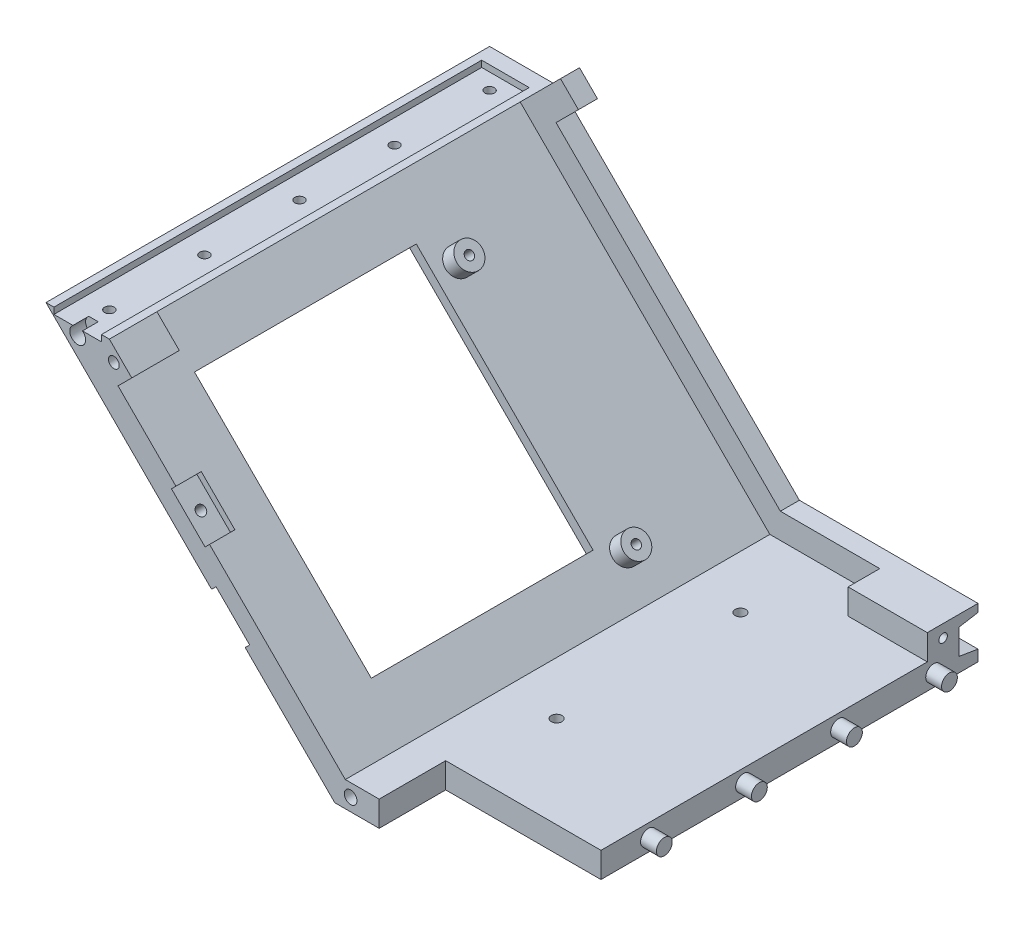
SolidWorks part; units mm, degrees
ref_plane "Plan de face" through (0, 0, 0) normal (0, 0, 1) x (1, 0, 0)
ref_plane "Plan de dessus" through (0, 0, 0) normal (0, 1, 0) x (1, 0, 0)
ref_plane "Plan de droite" through (0, 0, 0) normal (1, 0, 0) x (0, 0, -1)
sketch "Main-Sketch" plane through (0, 0, 0) normal (0, 0, 1) x (1, 0, 0)
  line L0 (0, 0) -> (0, 8)
  line L1 (0, 8) -> (-59.6863, 8)
  line L2 (-59.6863, 8) -> (-138.4931, 86.8069)
  line L3 (-154.15, 91.15) -> (-134.15, 91.15)
  line L4 (-154.15, 91.15) -> (-63, 0)
  line L5 (-63, 0) -> (0, 0)
  line L8 (-134.15, 91.15) -> (-138.4931, 86.8069)
  dimension "D1" = 8
  dimension "D2" = 8
  dimension "D3" = 63
  dimension "D4" = 135
  dimension "D5" = 20
  dimension "D6" = 154.15
extrude "Main-Extrusion" add sketch "Main-Sketch" along normal blind 140
sketch "Lcd-Sketch" plane through (0, 0, 0) normal (0, -1, 0) x (1, 0, 0)
  line L1 (0, 140) -> (-49, 140)
  line L2 (0, 140) -> (0, 119)
  line L3 (0, 119) -> (-49, 119)
  line L4 (-49, 140) -> (-49, 119)
  dimension "D1" = 21
  dimension "D2" = 49
extrude "Lcd-Hole" cut sketch "Lcd-Sketch" against normal through all
sketch "MotorBoard-Hole-Sketch" plane through (-31.5, -31.5, 0) normal (-0.7071, -0.7071, 0) x (0, 0, 1)
  line L0 (0, 173.4533) -> (0, 44.5477) construction
  line L1 (120, 143.4533) -> (50, 143.4533)
  line L2 (120, 143.4533) -> (120, 64.5477)
  line L3 (120, 64.5477) -> (50, 64.5477)
  line L4 (50, 143.4533) -> (50, 64.5477)
  line L5 (140, 173.4533) -> (140, 44.5477) construction
  line L6 (140, 173.4533) -> (0, 173.4533) construction
  line L7 (140, 44.5477) -> (0, 44.5477) construction
  dimension "D1" = 50
  dimension "D2" = 20
  dimension "D3" = 30
  dimension "D4" = 20
extrude "MotorBoard-Hole" cut sketch "MotorBoard-Hole-Sketch" against normal through all
sketch "MotorBoard-Window-Sketch" plane through (-31.5, -31.5, 0) normal (-0.7071, -0.7071, 0) x (0, 0, 1)
  line L0 (120, 64.5477) -> (120, 143.4533) construction
  line L1 (128, 151.4533) -> (42, 151.4533)
  line L2 (128, 151.4533) -> (128, 56.5477)
  line L3 (128, 56.5477) -> (42, 56.5477)
  line L4 (42, 151.4533) -> (42, 56.5477)
  line L5 (120, 143.4533) -> (50, 143.4533) construction
  line L6 (50, 143.4533) -> (50, 64.5477) construction
  line L7 (50, 64.5477) -> (120, 64.5477) construction
  dimension "D1" = 8
  dimension "D2" = 8
  dimension "D3" = 8
  dimension "D4" = 8
extrude "MotorBoard-Window" cut sketch "MotorBoard-Window-Sketch" against normal blind 5
sketch "MotorBoard-Fix-Sketch" plane through (-25.8431, -25.8431, 0) normal (0.7071, 0.7071, 0) x (0, 0, -1)
  line L0 (-140, 47.8614) -> (-140, 159.3112) construction
  line L1 (-140, 47.8614) -> (0, 47.8614) construction
  circle A0 centre (-42.5, 60.8614) radius 4
  circle A1 centre (-42.5, 135.3614) radius 4
  dimension "D1" = 8
  dimension "D2" = 74.5
  dimension "D3" = 97.5
  dimension "D4" = 13
extrude "MotorBoard-Fix-Extrusion" add sketch "MotorBoard-Fix-Sketch" along normal blind 5
sketch "MotorBoard-Fix-Hole-Sketch" plane through (-22.3076, -22.3076, 0) normal (0.7071, 0.7071, 0) x (0, 0, -1)
  circle A0 centre (-42.5, 60.8614) radius 1.35
  circle A1 centre (-42.5, 135.3614) radius 1.35
  circle A2 centre (-42.5, 135.3614) radius 4 construction
  dimension "D1" = 2.7
extrude "MotorBoard-Fix-Hole" cut sketch "MotorBoard-Fix-Hole-Sketch" against normal through all
hole_wizard "Fraisage pour vis à tête fraisée M32" positions "Esquisse8" profile "Esquisse9" countersink size "M3" standard "Ansi Metric" end condition through all
sketch "Esquisse8" plane through (0, 0, 0) normal (0, -1, 0) x (-1, 0, 0)
  line L2 (63, -140) -> (49, -140) construction
  line L4 (63, -140) -> (63, 0) construction
  line L5 (0, -119) -> (0, 0) construction
  point P0 (43, -90)
  point P2 (43, -32)
  dimension "D1" = 58
  dimension "D2" = 20
  dimension "D3" = 50
  dimension "D4" = 43
sketch "Esquisse9" plane through (-43, 0, 90) normal (1, 0, 0) x (0, 0, -1)
  line L0 (0, 0) -> (0, 91.15)
  line L1 (0, 91.15) -> (1.7, 91.15)
  line L2 (1.7, 91.15) -> (1.7, 1.45)
  line L3 (1.7, 1.45) -> (3.15, 0)
  line L5 (3.15, 0) -> (0, 0)
  line L6 (-1.7, 1.45) -> (-3.15, 0) construction
  line L11 (0, -6.35) -> (0, 107.95) construction
  dimension "Diamètre du perçage jusqu'au prochain" = 3.4
  dimension "Profondeur du perçage jusqu'au prochain" = 91.15
  dimension "Diamètre du fraisage entrant" = 6.3
  dimension "Angle du fraisage entrant" = 90
sketch "Bottom-Reinforcement-Sketch" plane through (0, 0, 0) normal (0, 0, -1) x (-1, 0, 0)
  line L0 (0, 8) -> (0, 16)
  line L1 (0, 16) -> (56.3726, 16)
  line L2 (56.3726, 16) -> (127.1794, 86.8069)
  line L3 (127.1794, 86.8069) -> (120.1084, 93.8779)
  line L4 (120.1084, 93.8779) -> (125.7652, 99.5348)
  line L5 (125.7652, 99.5348) -> (138.4931, 86.8069)
  line L6 (138.4931, 86.8069) -> (59.6863, 8)
  line L7 (59.6863, 8) -> (0, 8)
  point P4 (138.4931, 86.8069)
  point P12 (118.4675, 105.9273)
  point P14 (105.4642, 93.374)
  point P15 (109.6976, 86.8069)
  point P16 (0, 0)
  point P17 (122.9622, 79.545)
  point P18 (50.4301, 16)
  point P19 (113.6488, 84.3428)
  dimension "D1" = 8
  dimension "D2" = 8
  dimension "D3" = 10
  dimension "D4" = 8
extrude "Bottom-Reinforcement-Extrusion" add sketch "Bottom-Reinforcement-Sketch" against normal blind 6 separate body
sketch "LeftFix-Sketch" plane through (0, 0, 0) normal (1, 0, 0) x (0, 0, -1)
  line L0 (0, 0) -> (0, 8) construction
  line L1 (-119, 8) -> (-119, 0) construction
  circle A0 centre (-104, 4) radius 2.5
  point P4 (0, 4)
  dimension "D2" = 5
  dimension "D1" = 15
extrude "LeftFix-Extrusion" add sketch "LeftFix-Sketch" along normal blind 5
pattern_linear "Répétition linéaire1" count 4 spacing 30 along (0, 0, -1) of "LeftFix-Extrusion"
ref_plane "EndOfBottomFix-Plan" through (-15, 0, 0) normal (1, 0, 0) x (0, 0, -1)
ref_axis "EndOfBottomFix-Axe" through (-15, 8, 6) along (0, 1, 0)
ref_plane "EndOfBottomFix-Inclined-Plan" through (-15.4952, 0, 4.1519) normal (0.9659, 0, -0.2588) x (0, 1, 0)
sketch "EndOfBottomFix-Sketch" plane through (0, 0, 0) normal (1, 0, 0) x (0, 0, -1)
  line L0 (0, 3.5) -> (-6, 4.5)
  line L1 (0, 16) -> (0, 8) construction
  line L2 (-6, 4.5) -> (-6, 12.5)
  line L3 (-6, 12.5) -> (0, 13.5)
  line L4 (0, 13.5) -> (0, 3.5)
  line L5 (-6, 16) -> (-6, 8) construction
  dimension "D1" = 2.5
  dimension "D2" = 10
  dimension "D3" = 8
extrude "EndOfBottomFix-Hole" cut sketch "EndOfBottomFix-Sketch" against normal up to surface (16.6077 mm away) up to plane "EndOfBottomFix-Inclined-Plan"
sketch "Bottom-Fix-Reinforcement-Sketch" plane through (0, 8, 0) normal (0, 1, 0) x (1, 0, 0)
  line L1 (0, -6) -> (-25, -6)
  line L2 (0, -6) -> (0, -16)
  line L3 (0, -16) -> (-25, -16)
  line L4 (-25, -6) -> (-25, -16)
  dimension "D1" = 25
  dimension "D2" = 10
extrude "Bottom-Fix-Reinforcement-Extrusion" add sketch "Bottom-Fix-Reinforcement-Sketch" along normal up to surface (8 mm away) up to face at (-28.1863, 16, 3)
sketch "Bottom-Fix-Left-Right-Sketch" plane through (-25, 0, 0) normal (1, 0, 0) x (0, 0, -1)
  line L0 (-16, 16) -> (-16, 8) construction
  line L1 (-6, 16) -> (-16, 16) construction
  circle A0 centre (-11, 12) radius 1.35
  point P4 (-16, 12)
  point P5 (0, 0)
  point P8 (-11, 16)
  dimension "D1" = 2.7
extrude "Bottom-Fix-Left-Right-Hole" cut sketch "Bottom-Fix-Left-Right-Sketch" along normal through all
sketch "Bottom-Top-Fix-Sketch" plane through (0, 0, 140) normal (0, 0, 1) x (1, 0, 0)
  line L0 (0, 8) -> (0, 0) construction
  line L1 (-49, 8) -> (-49, 0) construction
  line L2 (-134.15, 91.15) -> (-154.15, 91.15) construction
  circle A0 centre (-58, 4) radius 2
  circle A1 centre (-144.15, 87.15) radius 2.5
  point P2 (-144.15, 87.3057)
  point P6 (0, 4)
  point P13 (-49, 4)
  dimension "D1" = 4
  dimension "D3" = 5
  dimension "D2" = 5
  dimension "D4" = 4
  dimension "D5" = 10
extrude "Bottom-Top-Fix-Hole" cut sketch "Bottom-Top-Fix-Sketch" against normal blind 5
sketch "Upp-Fix-Sketch" plane through (0, 0, 140) normal (0, 0, 1) x (1, 0, 0)
  line L0 (-134.15, 91.15) -> (-138.4931, 86.8069)
  line L1 (-138.4931, 86.8069) -> (-131.4221, 79.7358)
  line L2 (-59.6863, 8) -> (-138.4931, 86.8069) construction
  line L3 (-131.4221, 79.7358) -> (-127.0789, 84.0789)
  line L4 (-127.0789, 84.0789) -> (-134.15, 91.15)
  dimension "D1" = 10
extrude "Up-Fix-Extrusion" add sketch "Upp-Fix-Sketch" against normal blind 15
hole_wizard "Fraisage pour vis à tête fraisée M31" positions "Esquisse7" profile "Esquisse6" countersink size "M3" standard "Ansi Metric" end condition up to next
sketch "Esquisse7" plane through (0, 0, 125) normal (0, 0, -1) x (-1, 0, 0)
  line L0 (127.0789, 84.0789) -> (134.15, 91.15) construction
  line L1 (131.4221, 79.7358) -> (127.0789, 84.0789) construction
  point P0 (132.7358, 85.4931)
  dimension "D1" = 3
  dimension "D2" = 5
sketch "Esquisse6" plane through (-132.7358, 85.4931, 125) normal (1, 0, 0) x (0, 1, 0)
  line L0 (0, 0) -> (0, 15)
  line L1 (0, 15) -> (1.7, 15)
  line L2 (1.7, 15) -> (1.7, 1.3)
  line L3 (1.7, 1.3) -> (3, 0)
  line L5 (3, 0) -> (0, 0)
  line L6 (-1.7, 1.3) -> (-3, 0) construction
  line L11 (0, -6.35) -> (0, 107.95) construction
  dimension "Diamètre du perçage jusqu'au prochain" = 3.4
  dimension "Profondeur du perçage jusqu'au prochain" = 15
  dimension "Diamètre du fraisage entrant" = 6
  dimension "Angle du fraisage entrant" = 90
sketch "Reinforcement-Left-Sketch" plane through (0, 91.15, 0) normal (0, 1, 0) x (1, 0, 0)
  line L0 (-154.15, -140) -> (-154.15, 0) construction
  line L1 (-136.65, -140) -> (-151.65, -140)
  line L2 (-136.65, -140) -> (-136.65, -5)
  line L3 (-136.65, -5) -> (-151.65, -5)
  line L4 (-151.65, -140) -> (-151.65, -5)
  line L8 (-134.15, 0) -> (-154.15, 0) construction
  line L9 (-134.15, -140) -> (-154.15, -140) construction
  point P6 (-151.65, -140)
  point P8 (-151.65, 0)
  point P9 (-151.65, -4.1547)
  point P11 (0, 0)
  dimension "D1" = 2.5
  dimension "D2" = 15
  dimension "D4" = 5
extrude "Reinforcement-Left-Hole" cut sketch "Reinforcement-Left-Sketch" against normal blind 2
sketch "Reinforcement-Left-Fix-Sketch" plane through (0, 89.15, 0) normal (0, 1, 0) x (1, 0, 0)
  line L6 (-136.65, -140) -> (-136.65, -5) construction
  line L7 (-142.65, -140) -> (-136.65, -140) construction
  circle A0 centre (-144.15, -130) radius 1.5
  dimension "D1" = 7.5
  dimension "D3" = 3
  dimension "D2" = 10
extrude "Reinforcement-Left-Fix-Hole" cut sketch "Reinforcement-Left-Fix-Sketch" against normal blind 6
pattern_linear "Reinforcement-Left-Fix-Linear-Repeat" count 5 spacing 30 along (0, 0, -1) of "Reinforcement-Left-Fix-Hole"
sketch "Reinforcement-Internal-Sketch" plane through (-25.8431, -25.8431, 0) normal (0.7071, 0.7071, 0) x (0, 0, -1)
  line L0 (-140, 47.8614) -> (-140, 149.3112) construction
  line L1 (-132, 108.4533) -> (-140, 108.4533)
  line L2 (-132, 108.4533) -> (-132, 123.4533)
  line L3 (-132, 123.4533) -> (-140, 123.4533)
  line L4 (-140, 108.4533) -> (-140, 123.4533)
  line L6 (-140, 173.4533) -> (0, 173.4533) construction
  dimension "D1" = 15
  dimension "D2" = 8
  dimension "D3" = 50
extrude "Reinforcement-Internal-Hole" cut sketch "Reinforcement-Internal-Sketch" against normal blind 2
sketch "Reinforcement-Internal-Fix-Sketch" plane through (-27.2574, -27.2574, 0) normal (0.7071, 0.7071, 0) x (0, 0, -1)
  line L0 (-132, 123.4533) -> (-140, 123.4533) construction
  line L1 (-132, 108.4533) -> (-132, 123.4533) construction
  circle A0 centre (-136, 115.9533) radius 1.5
  point P2 (0, 0)
  point P5 (-136, 123.4533)
  point P6 (0, 0)
  point P9 (-132, 115.9533)
  dimension "D1" = 3
extrude "Reinforcement-Internal-Fix-Hole" cut sketch "Reinforcement-Internal-Fix-Sketch" against normal blind 5
sketch "Reinforcement-External-Sketch" plane through (-31.5, -31.5, 0) normal (-0.7071, -0.7071, 0) x (0, 0, 1)
  line L0 (140, 173.4533) -> (140, 44.5477) construction
  line L1 (140, 99.5477) -> (132, 99.5477)
  line L2 (140, 99.5477) -> (140, 84.5477)
  line L3 (140, 84.5477) -> (132, 84.5477)
  line L4 (132, 99.5477) -> (132, 84.5477)
  line L5 (140, 44.5477) -> (0, 44.5477) construction
  point P6 (136, 84.5477)
  dimension "D1" = 15
  dimension "D2" = 40
  dimension "D3" = 8
extrude "Reinforcement-External-Hole" cut sketch "Reinforcement-External-Sketch" against normal blind 2
sketch "Reinforcement-External-Fix-Sketch" plane through (-30.0858, -30.0858, 0) normal (-0.7071, -0.7071, 0) x (0, 0, 1)
  line L0 (140, 84.5477) -> (140, 99.5477) construction
  line L1 (140, 99.5477) -> (132, 99.5477) construction
  circle A0 centre (136, 92.0477) radius 1.5
  point P4 (140, 92.0477)
  point P5 (0, 0)
  point P8 (136, 99.5477)
  dimension "D1" = 3
extrude "Reinforcement-External-Fix-Hole" cut sketch "Reinforcement-External-Fix-Sketch" against normal blind 5
